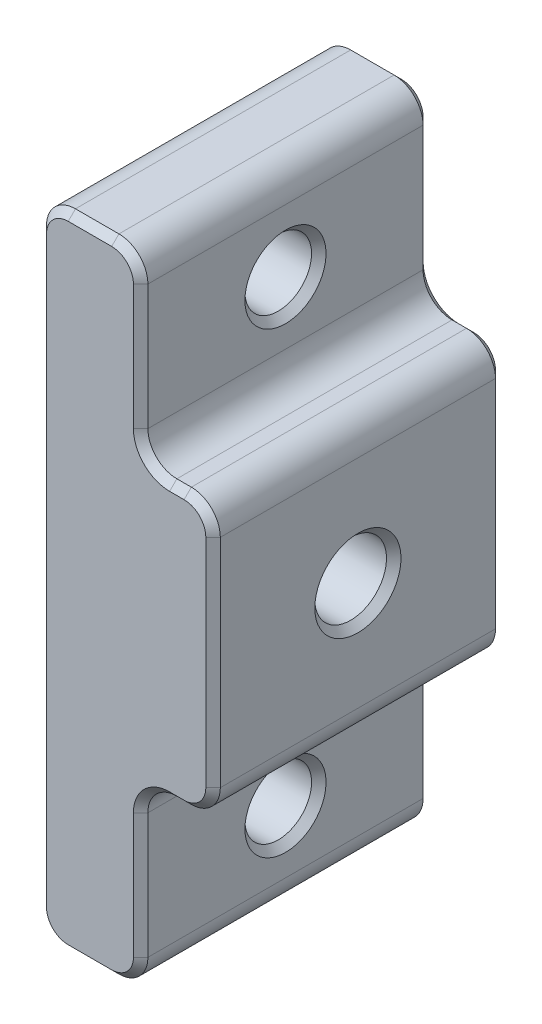
SolidWorks part; units mm, degrees
ref_plane "Front" through (0, 0, 0) normal (0, 0, 1) x (1, 0, 0)
ref_plane "Top" through (0, 0, 0) normal (0, 1, 0) x (1, 0, 0)
ref_plane "Right" through (0, 0, 0) normal (1, 0, 0) x (0, 0, -1)
sketch "Skizze1" plane through (0, 0, 0) normal (0, 0, 1) x (1, 0, 0)
  line L0 (0, 0) -> (19.3854, 0) construction
  line L1 (0, -22.1303) -> (0, 22.1303)
  line L2 (0, 22.1303) -> (7, 22.1303)
  line L3 (7, 22.1303) -> (7, 9.4858)
  line L4 (7, 9.4858) -> (12, 9.4858)
  line L5 (12, 9.4858) -> (12, -9.4858)
  line L6 (7, -9.4858) -> (12, -9.4858)
  line L7 (7, -22.1303) -> (7, -9.4858)
  line L8 (0, -22.1303) -> (7, -22.1303)
  point P9 (12, 0)
  dimension "D1" = 7
  dimension "D2" = 12
extrude "Aufsatz-Linear austragen1" add sketch "Skizze1" along normal blind 20
sketch "Skizze2" plane through (12, 0, 0) normal (1, 0, 0) x (0, 0, -1)
  line L0 (0, 0) -> (-20, 0) construction
  line L1 (-20, -9.4858) -> (-20, 9.4858) construction
  circle A0 centre (-10, 0) radius 2.475
  dimension "D1" = 4.95
extrude "Schnitt-Linear austragen1" cut sketch "Skizze2" against normal blind 20
sketch "Skizze3" plane through (0, 0, 0) normal (-1, 0, 0) x (0, 0, 1)
  circle A0 centre (10, 0) radius 4.75
  dimension "D1" = 9.5
extrude "Schnitt-Linear austragen2" cut sketch "Skizze3" against normal blind 6.55
sketch "Skizze4" plane through (7, 0, 0) normal (1, 0, 0) x (0, 0, -1)
  line L0 (-10, -9.4858) -> (-10, -22.1303) construction
  line L1 (-20, -9.4858) -> (0, -9.4858) construction
  line L2 (-20, -22.1303) -> (0, -22.1303) construction
  line L3 (0, 0) -> (-20, 0) construction
  line L4 (-20, -9.4858) -> (-20, 9.4858) construction
  circle A0 centre (-10, -15.8081) radius 2.3
  circle A1 centre (-10, 15.8081) radius 2.3
  dimension "D1" = 4.6
extrude "Schnitt-Linear austragen3" cut sketch "Skizze4" against normal blind 10
fillet "Verrundung1" radius 2 8 edges at (0, 22.1303, 10) (7, -9.4858, 10) (7, 22.1303, 10) (7, 9.4858, 10) (12, 9.4858, 10) (12, -9.4858, 10) (7, -22.1303, 10) (0, -22.1303, 10)
chamfer "Fase1" distance 0.5 angle 45 39 edges at (0, 15.8081, 7.7) (7, 15.8081, 12.3) (6.55, 0, 12.475) (12, 0, 7.525) (0, -15.8081, 7.7) (7, -15.8081, 7.7) (7, -15.8081, 20) (3.5, -22.1303, 20) (0, 0, 20) (3.5, 22.1303, 20) (7, 15.8081, 20) (9.5, 9.4858, 20) (12, 0, 20) (9.5, -9.4858, 20) (12, 0, 0) (9.5, 9.4858, 0) (7, 15.8081, 0) (3.5, 22.1303, 0) (0, 0, 0) (3.5, -22.1303, 0) (7, -15.8081, 0) (9.5, -9.4858, 0) (0, 0, 14.75) (6.4142, 21.5445, 20) (7.5858, 10.0716, 20) (11.4142, 8.9, 20) (11.4142, -8.9, 20) (7.5858, -10.0716, 20) (6.4142, -21.5445, 20) (0.5858, -21.5445, 20) (0.5858, 21.5445, 20) (0.5858, -21.5445, 0) (6.4142, -21.5445, 0) (7.5858, -10.0716, 0) (11.4142, -8.9, 0) (11.4142, 8.9, 0) (7.5858, 10.0716, 0) (6.4142, 21.5445, 0) (0.5858, 21.5445, 0)
